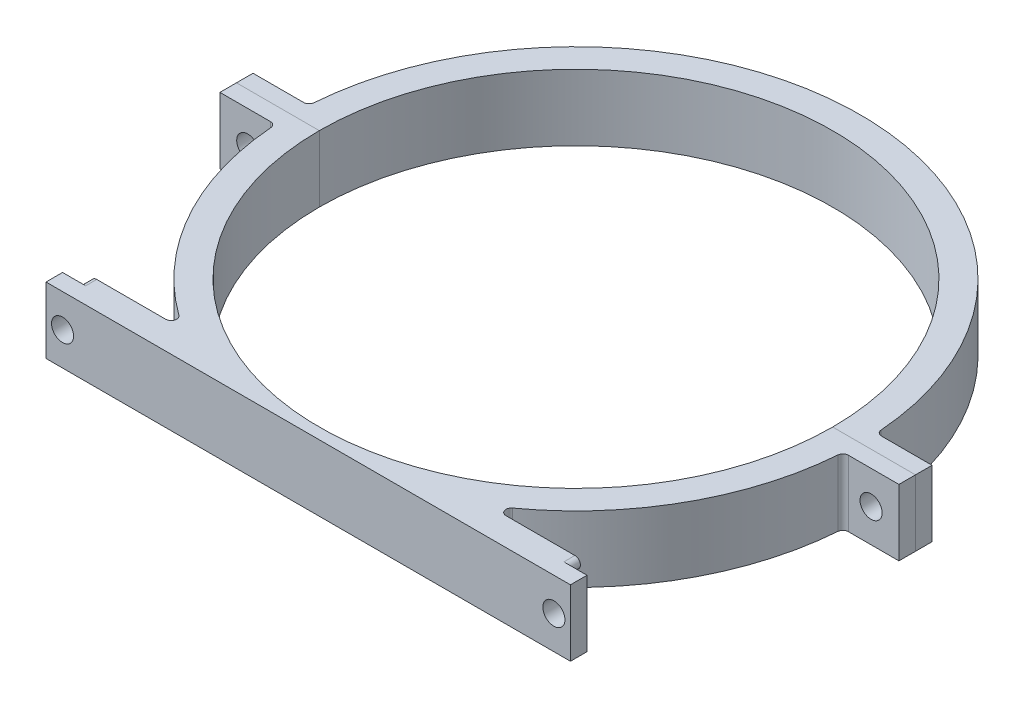
SolidWorks part; units mm, degrees
ref_plane "Front Plane" through (0, 0, 0) normal (0, 0, 1) x (1, 0, 0)
ref_plane "Top Plane" through (0, 0, 0) normal (0, 1, 0) x (1, 0, 0)
ref_plane "Right Plane" through (0, 0, 0) normal (1, 0, 0) x (0, 0, -1)
sketch "Sketch1" plane through (0, 0, 0) normal (0, 1, 0) x (1, 0, 0)
  line L0 (-51.5, 0) -> (-46.5, 0) construction
  line L1 (-46.5, 0) -> (46.5, 0) construction
  line L2 (46.5, 0) -> (51.5, 0) construction
  line L3 (51.5, 0) -> (61.5, 0) construction
  line L4 (61.5, -3) -> (61.5, 3)
  line L5 (61.5, 3) -> (51.4125, 3)
  line L6 (61.5, -3) -> (51.4125, -3)
  line L7 (0, -6.6) -> (0, 6.6) construction
  line L8 (-51.5, 0) -> (-61.5, 0) construction
  line L9 (-61.5, 3) -> (-51.4125, 3)
  line L10 (-61.5, -3) -> (-61.5, 3)
  line L11 (-61.5, -3) -> (-51.4125, -3)
  circle A0 centre (0, 0) radius 46.5
  arc A1 (51.4125, 3) -> (-51.4125, 3) centre (0, 0) ccw
  arc A2 (51.5, 0) -> (51.4125, 3) centre (0, 0) ccw construction
  circle A3 centre (0, 0) radius 51.5 construction
  arc A4 (51.4125, -3) -> (51.5, 0) centre (0, 0) ccw construction
  arc A5 (-51.4125, 3) -> (-51.5, 0) centre (0, 0) ccw construction
  arc A6 (-51.4125, -3) -> (51.4125, -3) centre (0, 0) ccw
  arc A7 (-51.5, 0) -> (-51.4125, -3) centre (0, 0) ccw construction
  point P8 (0, 0)
  point P14 (61.5, 0)
  dimension "D1" = 93
  dimension "D3" = 6
  dimension "D4" = 10
  dimension "D2" = 5
extrude "Boss-Extrude1" add sketch "Sketch1" along normal blind 12
sketch "Sketch2" plane through (0, 0, 3) normal (0, 0, 1) x (1, 0, 0)
  line L0 (-61.5, 6) -> (-51.4125, 6) construction
  line L1 (-61.5, 12) -> (-61.5, 0) construction
  line L2 (-51.4125, 12) -> (-51.4125, 0) construction
  line L3 (51.4125, 6) -> (61.5, 6) construction
  line L4 (51.4125, 12) -> (51.4125, 0) construction
  line L5 (61.5, 12) -> (61.5, 0) construction
  circle A0 centre (56.4563, 6) radius 2
  circle A1 centre (-56.4563, 6) radius 2
  dimension "D1" = 4
  dimension "D2" = 4
extrude "Cut-Extrude1" cut sketch "Sketch2" against normal blind 12
split "Split1" trim tools "Front Plane" bodies to split 102 resulting bodies 103 104
sketch "Sketch3" plane through (0, 12, 0) normal (0, 1, 0) x (1, 0, 0)
  line L0 (-47.5, -51.5) -> (47.5, -51.5)
  line L1 (-47.5, -51.5) -> (-47.5, -46.5)
  line L2 (-47.5, -46.5) -> (47.5, -46.5)
  line L3 (47.5, -46.5) -> (47.5, -51.5)
  arc A1 (-51.4125, -3) -> (51.4125, -3) centre (0, 0) ccw construction
  arc A2 (-46.5, 0) -> (46.5, 0) centre (0, 0) ccw construction
  point P0 (0, -46.5)
  point P3 (0, -51.5)
  point P9 (0, -46.5)
  dimension "D1" = 95
extrude "Boss-Extrude2" add sketch "Sketch3" against normal blind 12
other "Move Face1" flip direction yes face at (0, 6, 51.5) offset 3 parameters "D1"=3
other "Move Face2" face at (34.818, 6, 46.5) face at (-34.818, 6, 46.5) offset 3 parameters "D1"=3
sketch "Sketch4" plane through (0, 0, 43.5) normal (0, 0, -1) x (-1, 0, 0)
  line L0 (47.5, 6) -> (44.5, 6) construction
  line L1 (47.5, 0) -> (47.5, 12) construction
  circle A0 centre (44.5, 6) radius 2
  dimension "D2" = 4
  dimension "D1" = 3
extrude "Cut-Extrude2" cut sketch "Sketch4" against normal through all
sketch "Sketch5" plane through (0, 0, 43.5) normal (0, 0, -1) x (-1, 0, 0)
  line L1 (47.5, 12) -> (42.6946, 9.5694)
  line L2 (47.5, 0) -> (47.5, 12)
  line L3 (47.5, 0) -> (47.5, 12)
  line L4 (47.5, 0) -> (42.6946, 2.4306)
  arc A1 (42.6946, 2.4306) -> (42.6946, 9.5694) centre (44.5, 6) ccw construction
  circle A2 centre (44.5, 6) radius 4
  arc A3 (42.6946, 9.5694) -> (42.6946, 2.4306) centre (44.5, 6) ccw
  dimension "D1" = 2
  dimension "D2" = 0
extrude "Cut-Extrude3" cut sketch "Sketch5" against normal blind 2
mirror "Mirror1" about plane through (0, 0, 0) normal (1, 0, 0) of "Cut-Extrude3", "Cut-Extrude2"
fillet "Fillet1" radius 1 8 edges at (-51.4125, 6, 3) (51.4125, 6, 3) (47.5, 0, 44.5) (47.5, 12, 44.5) (-27.5681, 6, 43.5) (27.5681, 6, 43.5) (-47.5, 12, 44.5) (-47.5, 0, 44.5) tangent propagation no
fillet "Fillet2" radius 1 2 edges at (-51.4125, 6, -3) (51.4125, 6, -3)
